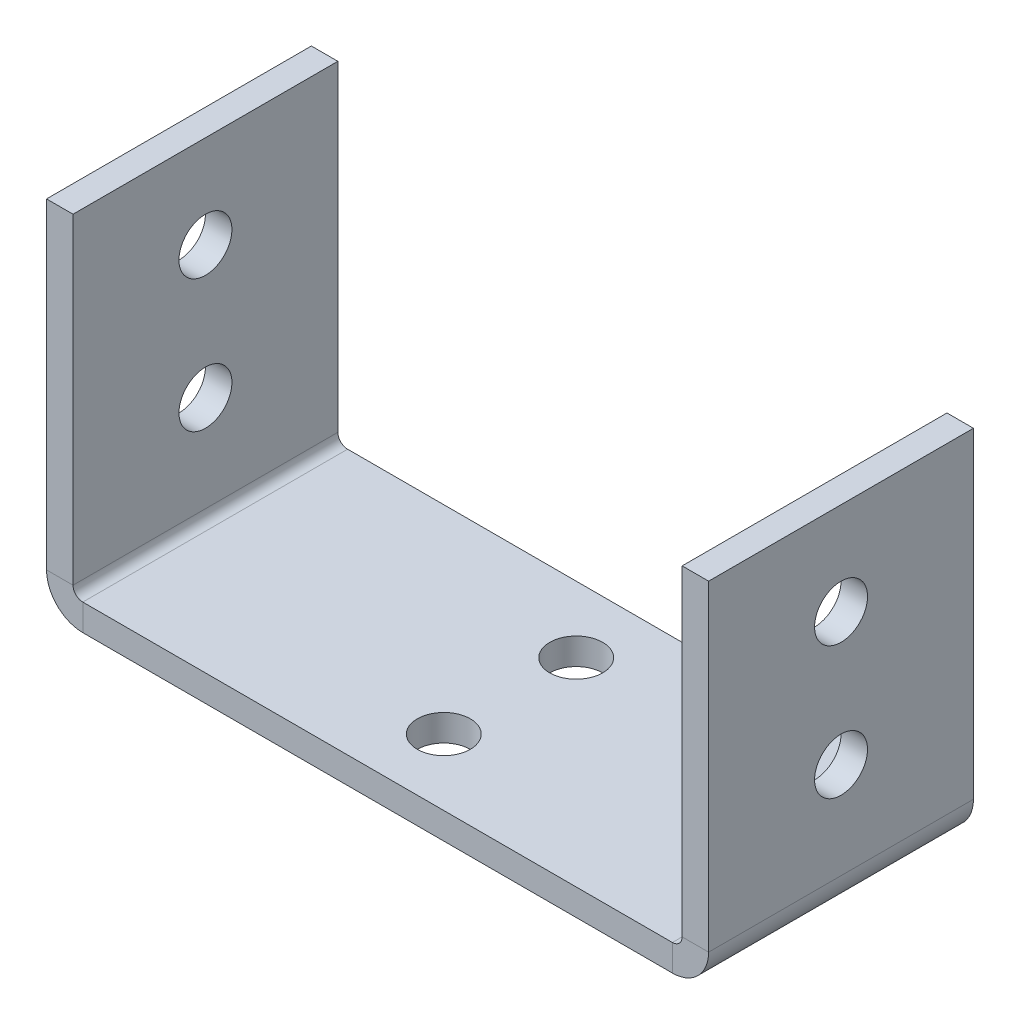
SolidWorks part; units mm, degrees
note: The reader was unsure of these and kept them because the rebuilt part matched: flange length of "Ребро-кромка1", "Ребро-кромка2".
ref_plane "Спереди" through (0, 0, 0) normal (0, 0, 1) x (1, 0, 0)
ref_plane "Сверху" through (0, 0, 0) normal (0, 1, 0) x (1, 0, 0)
ref_plane "Справа" through (0, 0, 0) normal (1, 0, 0) x (0, 0, -1)
sketch "Эскиз1" plane through (0, 0, 0) normal (0, 1, 0) x (1, 0, 0)
  line L8 (0, 0) -> (50, 0)
  line L9 (50, 0) -> (50, 20)
  line L10 (0, 20) -> (0, 0)
  line L11 (0, 20) -> (50, 20)
  dimension "D1" = 20
  dimension "D2" = 50
sheet metal parameters "Листовой металл1" thickness 2 parameters "D1"=0.7366
base flange "Базовая кромка1" sketch "Эскиз1" thickness 2 reverse thickness direction no parameters "D1"=0.7366
edge flange "Ребро-кромка1" sketch "Эскиз8" flange angle 90 flange length 27 flange position material inside bend radius 0.7366 thickness 2 relief rectangular parameters "D6"=10
sketch "Эскиз8" plane through (50, 0, 0) normal (1, 0, 0) x (0, 0, -1)
  line L2 (0, 0) -> (0, 25)
  line L3 (0, 25) -> (20, 25)
  line L4 (20, 25) -> (20, 0)
  line L7 (0, 0) -> (20, 0) construction
  line L8 (0, 0) -> (20, 0)
  dimension "D1" = 25
bend "EdgeBend1" bend radius 0.7366 bend angle 90 parameters "D5"=1
edge flange "Ребро-кромка2" sketch "Эскиз11" flange angle 90 flange length 27 flange position material inside bend radius 0.7366 thickness 2 relief rectangular parameters "D6"=10
sketch "Эскиз11" plane through (0, 0, 0) normal (-1, 0, 0) x (0, 0, 1)
  line L0 (-20, 0) -> (0, 0) construction
  line L1 (-20, 0) -> (0, 0)
  line L2 (-20, 0) -> (-20, 25)
  line L3 (-20, 25) -> (0, 25)
  line L4 (0, 25) -> (0, 0)
  dimension "D1" = 25
bend "EdgeBend2" bend radius 0.7366 bend angle 90 parameters "D5"=2
sketch "Эскиз12" plane through (0, -2, 0) normal (0, -1, 0) x (1, 0, 0)
  line L0 (25, 0) -> (25, -20) construction
  line L1 (2.7366, 0) -> (47.2634, 0) construction
  line L2 (47.2634, -20) -> (2.7366, -20) construction
  circle A0 centre (25, -5) radius 2
  circle A1 centre (25, -15) radius 2
  dimension "D1" = 4
  dimension "D2" = 5
  dimension "D3" = 5
extrude "Вырез-Вытянуть1" cut sketch "Эскиз12" against normal up to surface (2 mm away) normal cut yes up to face at (25, 0, -10)
sketch "Эскиз13" plane through (50, 0, 0) normal (1, 0, 0) x (0, 0, -1)
  line L0 (20, -2) -> (0, -2) construction
  line L1 (20, 0.7366) -> (20, 25) construction
  circle A0 centre (10, 8) radius 2
  circle A1 centre (10, 18) radius 2
  dimension "D1" = 10
  dimension "D4" = 4
  dimension "D2" = 10
  dimension "D3" = 10
extrude "Вырез-Вытянуть2" cut sketch "Эскиз13" against normal up to surface (50 mm away) normal cut yes up to face at (0, 12.8683, -10)
flat pattern "Развертка1" [suppressed]
sketch "Сгиб-Линии1" plane through (0, 0, 0) normal (0, 1, 0) x (1, 0, 0)
  line L0 (48.6273, 0) -> (48.6273, 20) construction
  line L1 (48.6273, 0) -> (48.6273, 20) construction
  line L2 (1.3727, 20) -> (1.3727, 0) construction
  line L3 (1.3727, 20) -> (1.3727, 0) construction
sketch3d "Граничная рамка1" [suppressed]
  line L0 (74.2546, 0, 0) -> (-24.2546, 0, 0) construction
  line L1 (74.2546, 20, 0) -> (-24.2546, 20, 0) construction
  line L2 (74.2546, 0, 0) -> (74.2546, 20, 0) construction
  line L3 (-24.2546, 0, 0) -> (-24.2546, 20, 0) construction
bend of the flat pattern "Плоское состояние-<EdgeBend1>1"
bend of the flat pattern "Плоское состояние-<EdgeBend2>1"
